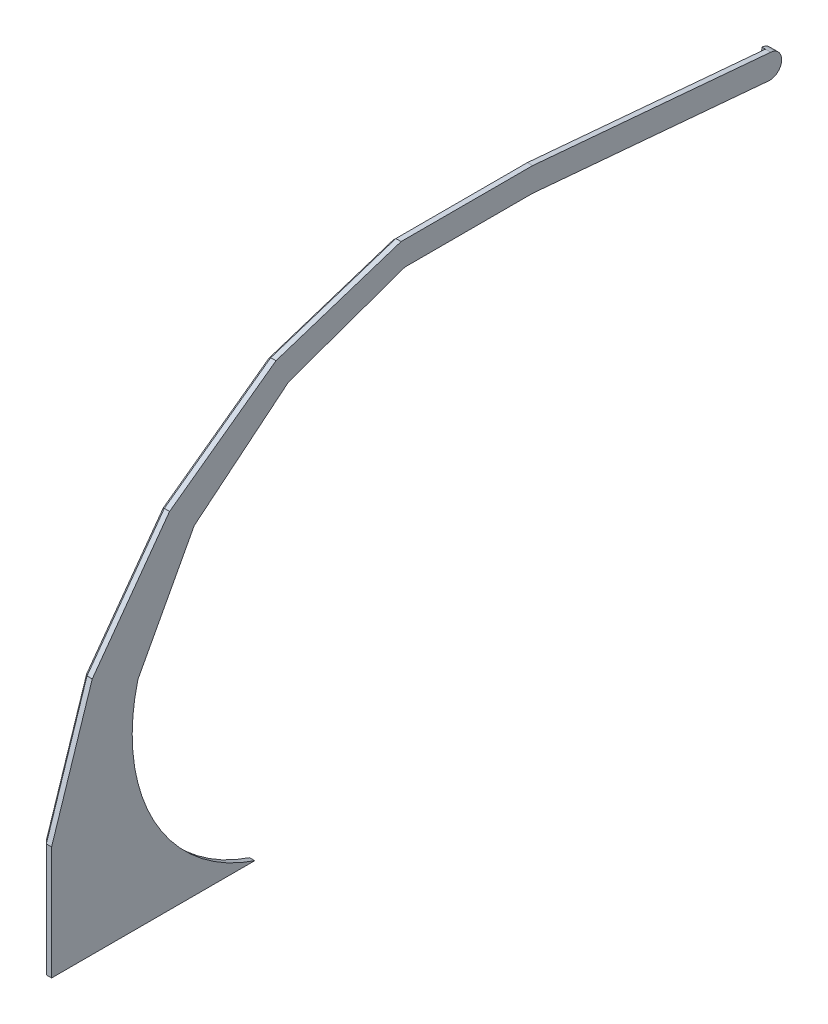
SolidWorks part; units mm, degrees
ref_plane "Front Plane" through (0, 0, 0) normal (0, 0, 1) x (1, 0, 0)
ref_plane "Top Plane" through (0, 0, 0) normal (0, 1, 0) x (1, 0, 0)
ref_plane "Right Plane" through (0, 0, 0) normal (1, 0, 0) x (0, 0, -1)
sketch "Sketch1" plane through (0, 0, 0) normal (1, 0, 0) x (0, 0, -1)
  line L0 (12.6153, -92.6333) -> (182.6153, -92.6333)
  line L6 (415.1195, 274.7215) -> (612.6153, 257.4428)
  line L8 (614.3584, 277.3667) -> (415.1195, 294.7979)
  line L9 (12.6153, -92.6333) -> (12.6153, 2.3615)
  line L10 (12.6153, 2.3615) -> (46.6281, 107.0421)
  line L11 (46.6281, 107.0421) -> (111.3243, 196.0888)
  line L12 (111.3243, 196.0888) -> (200.371, 260.7851)
  line L13 (200.371, 260.7851) -> (305.0517, 294.7979)
  line L14 (305.0517, 294.7979) -> (415.1195, 294.7979)
  line L15 (452.6153, 271.441) -> (183.2145, -92.6333) construction
  line L16 (452.6153, 271.441) -> (634.136, -92.6333) construction
  line L20 (84.8259, 87.5794) -> (131.9298, 175.4834)
  line L21 (131.9298, 175.4834) -> (210.8849, 240.1505)
  line L22 (210.8849, 240.1505) -> (308.2365, 274.69)
  line L23 (308.2365, 274.69) -> (415.1195, 274.7215)
  line L24 (111.3243, 196.0888) -> (131.9298, 175.4834) construction
  line L25 (200.371, 260.7851) -> (210.8849, 240.1505) construction
  line L26 (46.6281, 107.0421) -> (84.8259, 87.5794) construction
  line L27 (183.2145, -92.6333) -> (634.136, -92.6333) construction
  line L28 (305.0517, 294.7979) -> (308.2365, 274.69) construction
  arc A0 (84.8259, 87.5794) -> (182.6153, -92.6333) centre (230.5143, 49.9965) ccw
  arc A2 (612.6153, 257.4428) -> (614.3584, 277.3667) centre (613.4869, 267.4048) ccw
  dimension "D1" = 600
  dimension "D2" = 200
  dimension "D3" = 5
  dimension "D4" = 370
  dimension "D5" = 20
  dimension "D12" = 162
  dimension "D13" = 162
  dimension "D14" = 162
  dimension "D15" = 162
  dimension "D16" = 170
  dimension "D18" = 63
  dimension "D19" = 58.5
  dimension "D20" = 160
  dimension "D6" = 81
  dimension "D7" = 81
  dimension "D8" = 81
  dimension "D17" = 162
  dimension "D21" = 81
extrude "Boss-Extrude1" add sketch "Sketch1" against normal blind 4.4
sketch "Sketch2" plane through (-4.4, 0, 0) normal (-1, 0, 0) x (0, 0, 1)
  line L0 (-614.3584, 277.3667) -> (-614.0969, 274.3781)
  line L1 (-614.0969, 274.3781) -> (-415.1195, 291.7864)
  line L2 (-612.8768, 260.4314) -> (-415.25, 277.7215)
  line L3 (-612.8768, 260.4314) -> (-612.6153, 257.4428)
  line L4 (-415.1195, 294.7979) -> (-415.1195, 274.7215) construction
  line L5 (-305.0517, 294.7979) -> (-308.2365, 274.69) construction
  line L6 (-200.371, 260.7851) -> (-210.8849, 240.1505) construction
  line L7 (-415.1195, 291.7864) -> (-305.5287, 291.7864)
  line L8 (-415.25, 277.7215) -> (-307.7613, 277.6898)
  line L9 (-307.7613, 277.6898) -> (-209.5176, 242.8338)
  line L10 (-305.5287, 291.7864) -> (-201.7552, 258.0684)
  line L11 (-111.3243, 196.0888) -> (-131.9298, 175.4834) construction
  line L12 (-46.6281, 107.0421) -> (-84.8259, 87.5794) construction
  line L13 (-12.6153, 2.3615) -> (4.7357, 1.8595) construction
  line L14 (-201.7552, 258.0684) -> (-113.4803, 193.9329)
  line L15 (-113.4803, 193.9329) -> (-49.3448, 105.6579)
  line L16 (-49.3448, 105.6579) -> (-15.8118, 2.4539)
  line L17 (-15.8118, 2.4539) -> (-15.8118, -92.6333)
  line L18 (-12.6153, -92.6333) -> (-182.6153, -92.6333) construction
  line L19 (-15.8118, -92.6333) -> (-101.9058, -92.6333)
  line L20 (-101.9058, -92.6333) -> (-66.1481, 3.9103)
  line L21 (-66.1481, 3.9103) -> (-82.1529, 88.9413)
  line L22 (-82.1529, 88.9413) -> (-129.839, 177.5741)
  line L23 (-129.839, 177.5741) -> (-209.5176, 242.8338)
  line L26 (-415.1195, 294.7979) -> (-305.0517, 294.7979) construction
  line L27 (-308.2365, 274.69) -> (-415.1195, 274.7215) construction
  line L28 (-614.3584, 277.3667) -> (-415.1195, 294.7979) construction
  line L29 (-415.1195, 274.7215) -> (-612.6153, 257.4428) construction
  line L30 (-305.0517, 294.7979) -> (-200.371, 260.7851) construction
  line L31 (-210.8849, 240.1505) -> (-308.2365, 274.69) construction
  line L32 (-200.371, 260.7851) -> (-111.3243, 196.0888) construction
  line L33 (-131.9298, 175.4834) -> (-210.8849, 240.1505) construction
  line L34 (-111.3243, 196.0888) -> (-46.6281, 107.0421) construction
  line L36 (-46.6281, 107.0421) -> (-12.6153, 2.3615) construction
  line L37 (-12.6153, 2.3615) -> (-12.6153, -92.6333) construction
  line L39 (-563.8078, 273.2568) -> (-553.2482, 274.1807)
  line L40 (-563.8078, 273.2568) -> (-563.4941, 269.6705)
  line L41 (-563.4941, 269.6705) -> (-552.9344, 270.5944)
  line L42 (-553.2482, 274.1807) -> (-552.9344, 270.5944)
  line L43 (-473.5526, 281.1532) -> (-462.9929, 282.077)
  line L44 (-473.5526, 281.1532) -> (-473.2388, 277.5669)
  line L45 (-473.2388, 277.5669) -> (-462.6792, 278.4907)
  line L46 (-462.9929, 282.077) -> (-462.6792, 278.4907)
  line L47 (-618.9236, 268.736) -> (-608.3639, 269.6598)
  line L48 (-618.9236, 268.736) -> (-618.6098, 265.1497)
  line L49 (-618.6098, 265.1497) -> (-608.0501, 266.0735)
  line L50 (-608.3639, 269.6598) -> (-608.0501, 266.0735)
  arc A0 (-614.3584, 277.3667) -> (-612.6153, 257.4428) centre (-613.4869, 267.4048) ccw
  dimension "D1" = 3
  dimension "D2" = 3
  dimension "D3" = 3.6
  dimension "D4" = 10.6
  dimension "D5" = 50
  dimension "D6" = 3.6
  dimension "D7" = 10.6
  dimension "D8" = 80
  dimension "D9" = 8.5
  dimension "D10" = 8.5
  dimension "D11" = 10.6
  dimension "D12" = 5.3
  dimension "D13" = 3.6
  dimension "D14" = 1.8
  dimension "D15" = 3
  dimension "D16" = 3
extrude "Boss-Extrude2" add sketch "Sketch2" along normal blind 3
equation "\"Phone height\"= 370"
equation "\"edge distance from wall\"= 600"
equation "\"phone angle\"= 5"
equation "\"D1@Sketch1\"=\"edge distance from wall\""
equation "\"base depth\"= 170"
equation "\"width\"= 108"
equation "\"Phone segment length\"= 200"
equation "\"D2@Sketch1\"=\"Phone segment length\""
equation "\"D3@Sketch1\"=\"phone angle\""
equation "\"D4@Sketch1\"=\"Phone height\""
equation "\"Phone segment thick\"= 20"
equation "\"D5@Sketch1\"=\"Phone segment thick\""
equation "\"Phone segment acute angle\"= 1"
equation "\"D16@Sketch1\"=\"base depth\""
equation "\"upper segment count\"= 6"
equation "\"lower segment count\"= 5"
equation "\"upper segment angle\"= 180 - ( 90 / ( \"upper segment count\" - 1 ) )"
equation "\"D12@Sketch1\"=\"upper segment angle\""
equation "\"D13@Sketch1\"=\"upper segment angle\""
equation "\"D14@Sketch1\"=\"upper segment angle\""
equation "\"D15@Sketch1\"=\"upper segment angle\""
equation "\"lower segment angle\"= 180 - ( 90 / ( \"lower segment count\" - 1 ) )"
equation "\"fov\"=63"
equation "\"D18@Sketch1\"=\"fov\""
equation "\"D19@Sketch1\"=(180-\"fov\")/2"
equation "\"D6@Sketch1\"=\"upper segment angle\"/2"
equation "\"D7@Sketch1\"=\"upper segment angle\"/2"
equation "\"D8@Sketch1\"=\"upper segment angle\"/2"
equation "\"D17@Sketch1\"=\"upper segment angle\""
equation "\"D21@Sketch1\"=\"upper segment angle\"/2"
equation "\"Thicker acrylic\"= 4.4"
equation "\"Thinner acrylic\"= 3"
equation "\"D1@Boss-Extrude1\"=\"Thicker acrylic\""
equation "\"D1@Sketch2\"=\"Thinner acrylic\""
equation "\"D2@Sketch2\"=\"Thinner acrylic\""
equation "\"phone thick\"= 8.5"
equation "\"phone support width\"= 10"
equation "\"fit\"= 0.6"
equation "\"D3@Sketch2\"=\"Thinner acrylic\"+\"fit\""
equation "\"D4@Sketch2\"=\"phone support width\"+\"fit\""
equation "\"D5@Sketch2\"=50"
equation "\"D6@Sketch2\"=\"Thinner acrylic\"+\"fit\""
equation "\"D7@Sketch2\"=\"phone support width\"+\"fit\""
equation "\"D9@Sketch2\"=\"phone thick\""
equation "\"D10@Sketch2\"=\"phone thick\""
equation "\"D1@Boss-Extrude2\"=\"Thinner acrylic\""
equation "\"D11@Sketch2\"=\"phone support width\"+\"fit\""
equation "\"D12@Sketch2\"=\"D11@Sketch2\"/2"
equation "\"D13@Sketch2\"=\"Thinner acrylic\"+\"fit\""
equation "\"D14@Sketch2\"=\"D13@Sketch2\"/2"
equation "\"phone support length\"= 98.5"
equation "\"D15@Sketch2\"=\"Thinner acrylic\""
equation "\"D16@Sketch2\"=\"Thinner acrylic\""
